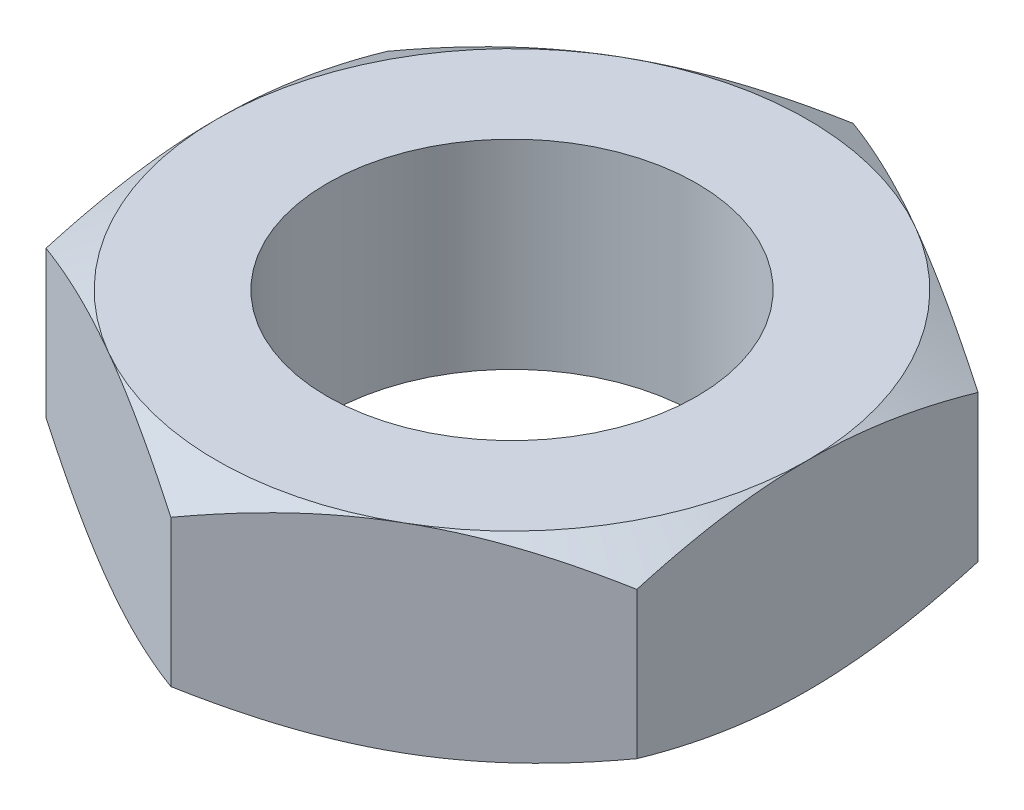
SolidWorks part; units mm, degrees
ref_plane "Front Plane" through (0, 0, 0) normal (0, 0, 1) x (1, 0, 0)
ref_plane "Top Plane" through (0, 0, 0) normal (0, 1, 0) x (1, 0, 0)
ref_plane "Right Plane" through (0, 0, 0) normal (1, 0, 0) x (0, 0, -1)
sketch "Sketch0" plane through (0, 0, 0) normal (0, 1, 0) x (1, 0, 0)
  line L0 (0, 0) -> (0, 2.5) construction
  line L1 (-4, 2.3094) -> (-4, -2.3094)
  line L2 (-4, -2.3094) -> (0, -4.6188)
  line L3 (0, -4.6188) -> (4, -2.3094)
  line L4 (4, -2.3094) -> (4, 2.3094)
  line L5 (4, 2.3094) -> (0, 4.6188)
  line L6 (0, 4.6188) -> (-4, 2.3094)
  line L7 (0, 0) -> (0, -2.5) construction
  line L8 (0, 0) -> (1.7678, -1.7678) construction
  circle A0 centre (0, 0) radius 4 construction
  circle A1 centre (0, 0) radius 2.5
  point P12 (0, 2.5)
  point P14 (0, -2.5)
  point P15 (-4, 2.3094)
  point P16 (4, 2.3094)
  point P17 (0, -2.5)
  point P19 (1.7678, -1.7678)
  dimension "Thread Size" = 5
  dimension "D1" = 45
  dimension "Hex" = 8
extrude "Boss-Extrude1" add sketch "Sketch0" along normal mid plane 2.7
sketch "Sketch1" plane through (0, 0, 0) normal (1, 0, 0) x (0, 0, -1)
  line L0 (2.5, -1.35) -> (2.5, 1.35) construction
  line L1 (-2.3094, -1.35) -> (-4.6188, -1.35) construction
  line L2 (2.5, -1.35) -> (2.5, 1.35) construction
  line L3 (-4.6188, 1.35) -> (-4.6188, -1.35) construction
  line L4 (-2.5541, -1.3187) -> (-2.5541, -1.8188) construction
  line L5 (-2.5541, -1.8188) -> (-2.1211, -1.5687) construction
  line L6 (-2.1211, -1.5687) -> (-2.5541, -1.3187) construction
  line L7 (-2.1211, -1.5687) -> (-2.1752, -1.5687) construction
  line L8 (-2.5, -1.35) -> (-2.5, -1.7875) construction
  line L9 (-2.1752, -1.5375) -> (-2.1752, -1.6) construction
  line L10 (-2.5, -1.5687) -> (-2.5541, -1.5687) construction
  line L11 (-2.5271, -1.3344) -> (-2.5271, -1.8031) construction
  line L12 (-4.6188, 1.35) -> (-4.6188, -1.35)
  line L13 (4.6188, 1.35) -> (4.6188, -1.35) construction
  line L14 (4.6188, 1.35) -> (4.6188, -1.35)
  point P14 (-2.5271, -1.5687)
  point P17 (-2.5271, -1.5687)
  dimension "D1" = 60
  dimension "Pitch" = 0.5
  dimension "D3" = 0.0625
sketch "Sketch5" plane through (0, 1.35, 0) normal (0, 1, 0) x (1, 0, 0)
  circle A0 centre (0, 0) radius 4 construction
  circle A1 centre (0, 0) radius 4
extrude "Cut-Extrude2" cut sketch "Sketch5" against normal through all draft 60 flip side to cut
mirror "Mirror2" about plane through (0, 0, 0) normal (0, 1, 0) of "Cut-Extrude2"
sketch "Sketch2" plane through (0, 1.35, 0) normal (0, 1, 0) x (1, 0, 0)
  circle A0 centre (0, 0) radius 2.5 construction
  circle A1 centre (0, 0) radius 2.5
sketch "Sketch6" [suppressed] plane through (0, 0, 0) normal (1, 0, 0) x (0, 0, -1)
  line L0 (-2.5271, -1.3344) -> (-2.5271, -1.8031)
  line L1 (-2.5271, -1.8031) -> (-2.1752, -1.6)
  line L2 (-2.1752, -1.6) -> (-2.1752, -1.5375)
  line L3 (-2.1752, -1.5375) -> (-2.5271, -1.3344)
sketch "Sketch7" [suppressed] plane through (0, 1.35, 0) normal (0, 1, 0) x (1, 0, 0)
  circle A2 centre (0, 0) radius 2.6
  circle A3 centre (0, 0) radius 2.6
  dimension "D1" = 0.1
ref_plane "Plane1" [suppressed] through (0, 4.35, 0) normal (0, 1, 0) x (1, 0, 0)
sketch "Sketch8" [suppressed] plane through (0, 4.35, 0) normal (0, 1, 0) x (1, 0, 0)
  circle A0 centre (0, 0) radius 2.5 construction
  circle A1 centre (0, 0) radius 2.5
curve "Helix/Spiral1" [suppressed] pitch 0.5 height 3.7 turns 7.4
sweep "Sweep1" [suppressed] add profiles "Sketch6" path "Helix/Spiral1"
sketch "Sketch9" [suppressed] plane through (0, -1.35, 0) normal (0, -1, 0) x (1, 0, 0)
  circle A0 centre (0, 0) radius 2.5 construction
  circle A1 centre (0, 0) radius 2.5 construction
  circle A2 centre (0, 0) radius 2.6
  dimension "D1" = 0.1
extrude "Cut-Extrude3" [suppressed] cut sketch "Sketch9" against normal through all draft 45 and the other way through all draft 45
mirror "Mirror3" [suppressed] about plane through (0, 0, 0) normal (0, 1, 0)
equation "\"D3@Helix/Spiral1\"=\"Height@Boss-Extrude1\"+(2*\"Pitch@Sketch1\")"
equation "\"D3@Sketch1\" = \"Pitch@Sketch1\" / 8"
equation "\"D4@Helix/Spiral1\"=\"Pitch@Sketch1\""
